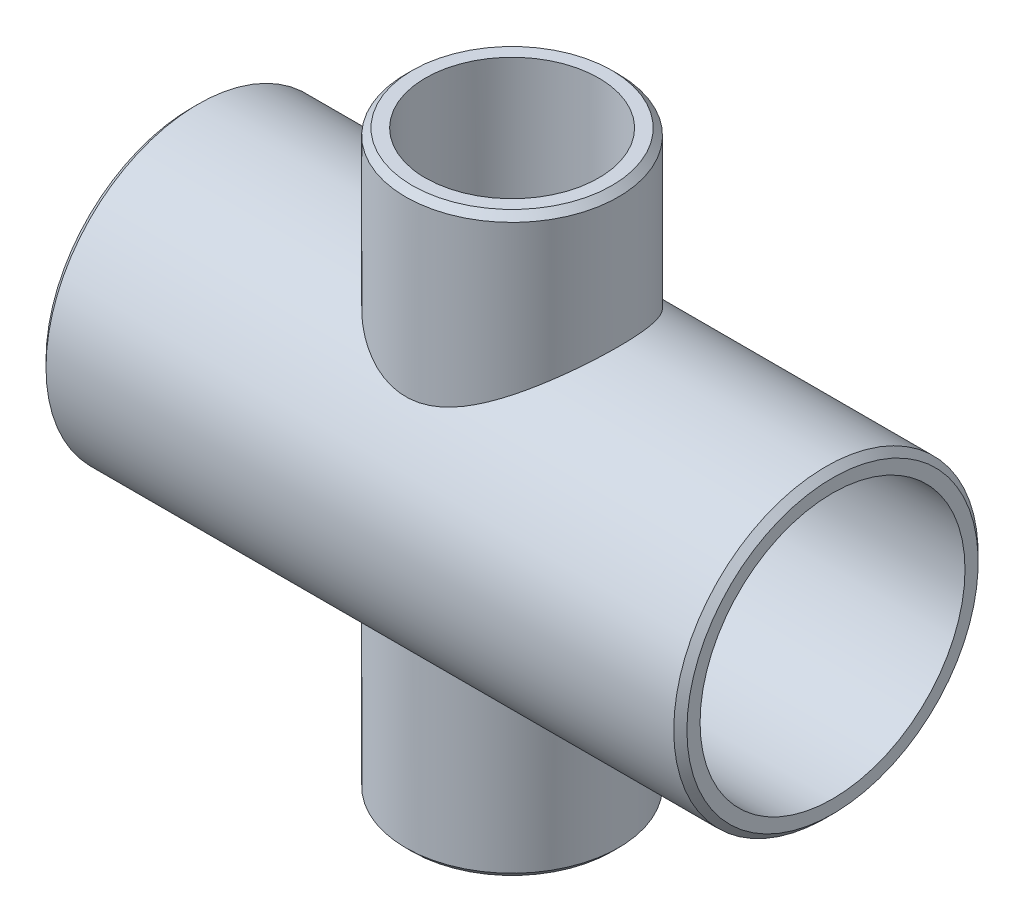
SolidWorks part; units mm, degrees
note: '?' marks a value the reader was unsure of.
ref_plane "front" through (0, 0, 0) normal (0, 0, 1) x (1, 0, 0)
ref_plane "top" through (0, 0, 0) normal (0, 1, 0) x (1, 0, 0)
ref_plane "side" through (0, 0, 0) normal (1, 0, 0) x (0, 0, -1)
other "Configuration Table"
sketch "RunRoute" plane through (0, 0, 0) normal (1, 0, 0) x (0, 0, -1)
  circle A0 centre (0, 0) radius 30.1625
  dimension "Diameter" = 60.325
extrude "RunExtrude" add sketch "RunRoute" along normal blind 63.5
mirror "RunExtrudeMirror" about plane through (0, 0, 0) normal (1, 0, 0) of "RunExtrude"
sketch "OutletRoute" plane through (0, 0, 0) normal (0, 1, 0) x (1, 0, 0)
  circle A0 centre (0, 0) radius 21.082
  dimension "Diameter" = 42.164
extrude "OutletExtrude" add sketch "OutletRoute" along normal blind 57.15
mirror "OutletExtrudeMirror" about plane through (0, 0, 0) normal (0, 1, 0) of "OutletExtrude"
shell "CrossShell" thickness 3.9116
chamfer "CrossChamfer" distance 1.3039 4 edges at (0, -57.15, 21.082) (63.5, 0, -30.1625) (-63.5, 0, -30.1625) (0, 57.15, 21.082)
sketch "Sketch1" plane through (0, 0, 0) normal (0, 0, 1) x (1, 0, 0)
  line L0 (-17.1704, -57.15) -> (17.1704, -57.15) construction
  line L1 (63.5, -26.2509) -> (63.5, 26.2509) construction
  line L2 (17.1704, 57.15) -> (-17.1704, 57.15) construction
  line L3 (-63.5, 26.2509) -> (-63.5, -26.2509) construction
  line L6 (62.1961, 0) -> (-62.1961, 0) construction
  line L7 (0, 55.8461) -> (0, 21.5715) construction
  point P0 (0, 57.15)
  point P1 (63.5, 0)
  point P2 (0, -57.15)
  point P3 (-63.5, 0)
  point P12 (0, 0)
other "CPoint1" parameters "Diameter"=31.75, "StubLength"=0
ref_axis "Axis1" through (0, -67.15, 0) along (0, 1, 0)?
other "CPoint2" parameters "Diameter"=50.8, "StubLength"=0
ref_axis "Axis2" through (73.5, 0, 0) along (-1, 0, 0)?
other "CPoint3" parameters "Diameter"=31.75, "StubLength"=0
ref_axis "Axis3" through (0, 67.15, 0) along (0, -1, 0)?
other "CPoint4" parameters "Diameter"=50.8, "StubLength"=0
ref_axis "Axis4" through (-73.5, 0, 0) along (1, 0, 0)?
other "RPoint1"
equation "\"ChamferDistance@CrossChamfer\" = \"WallThickness@CrossShell\" / 3"
